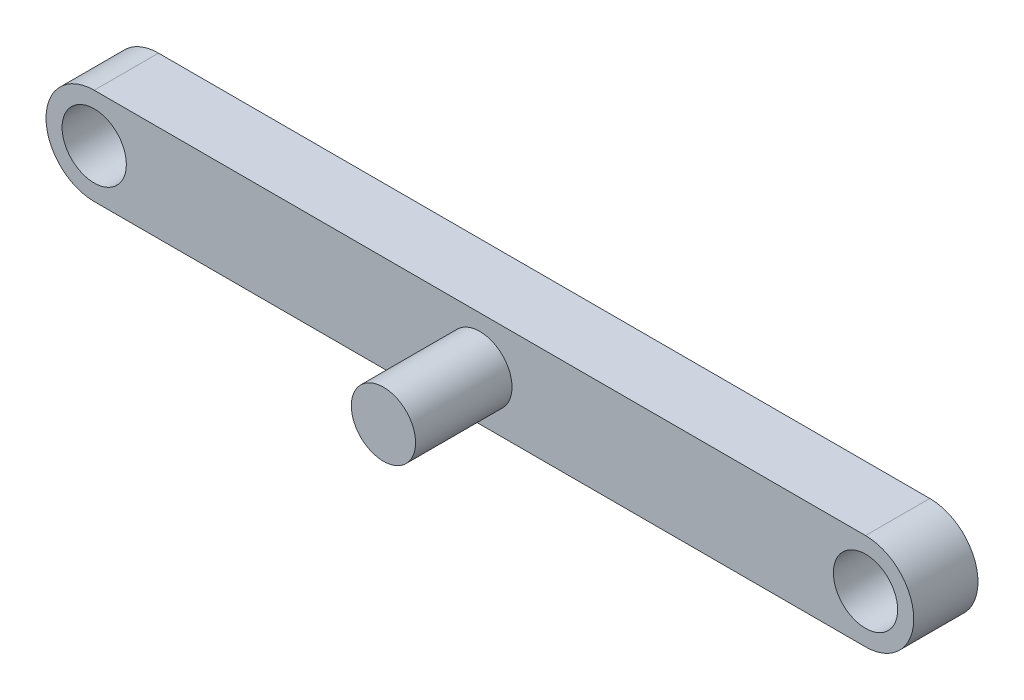
SolidWorks part; units mm, degrees
ref_plane "Front Plane" through (0, 0, 0) normal (0, 0, 1) x (1, 0, 0)
ref_plane "Top Plane" through (0, 0, 0) normal (0, 1, 0) x (1, 0, 0)
ref_plane "Right Plane" through (0, 0, 0) normal (1, 0, 0) x (0, 0, -1)
sketch "Sketch1" plane through (0, 0, 0) normal (0, 0, 1) x (1, 0, 0)
  line L0 (-177.3809, 0) -> (164.1188, 0) construction
  line L1 (-24, 0) -> (24, 0) construction
  line L2 (-24, 3) -> (24, 3)
  line L3 (-24, -3) -> (24, -3)
  arc A0 (-24, 3) -> (-24, -3) centre (-24, 0) ccw
  arc A1 (24, -3) -> (24, 3) centre (24, 0) ccw
  circle A2 centre (-24, 0) radius 2
  circle A3 centre (24, 0) radius 2
  circle A4 centre (0, 0) radius 2
  point P5 (0, 0)
  dimension "D1" = 48
  dimension "D2" = 3
extrude "Boss-Extrude2" add sketch "Sketch1" along normal blind 4
extrude "Boss-Extrude3" add sketch "Sketch1<2>" along normal blind 10 contours A4 region at (0, 0, 0)
sketch "Sketch1<2>" plane through (0, 0, 0) normal (0, 0, 1) x (1, 0, 0) same geometry as "Sketch1"
